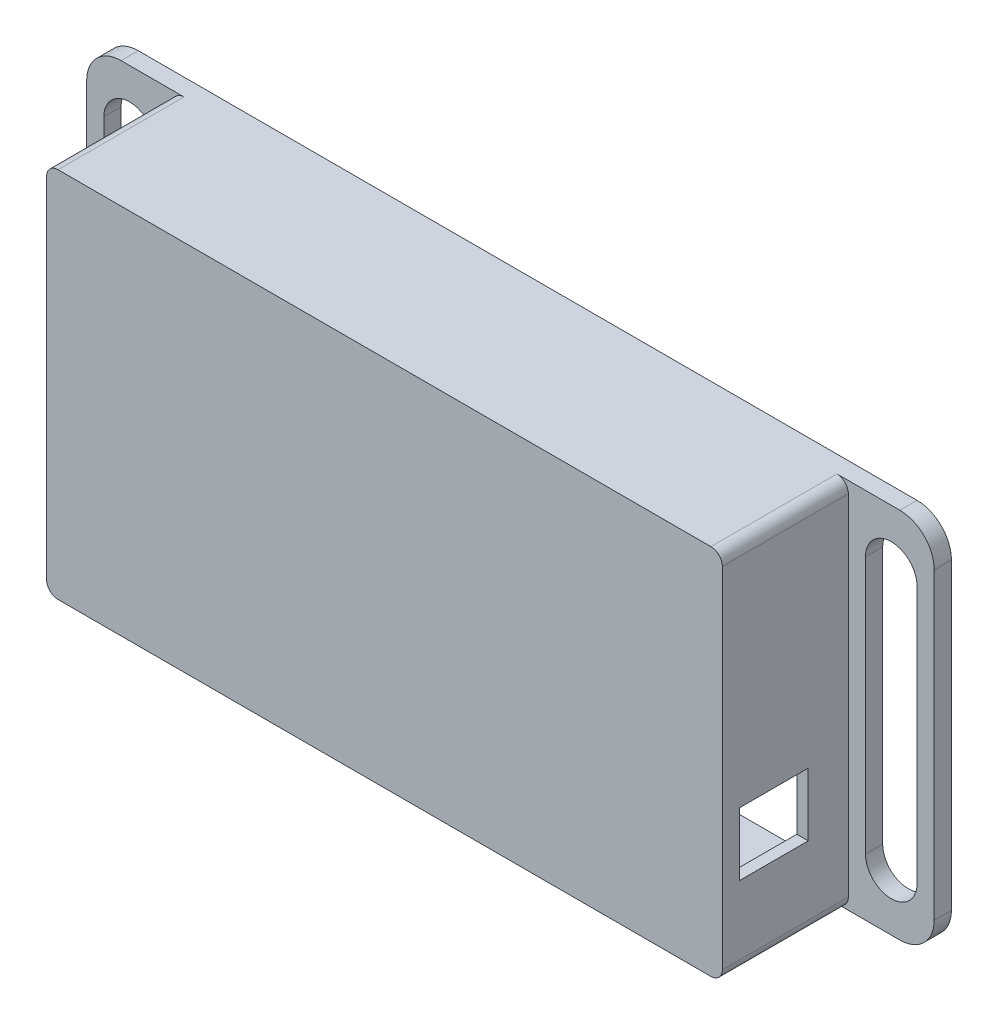
SolidWorks part; units mm, degrees
ref_plane "Front" through (0, 0, 0) normal (0, 0, 1) x (1, 0, 0)
ref_plane "Top" through (0, 0, 0) normal (0, 1, 0) x (1, 0, 0)
ref_plane "Right" through (0, 0, 0) normal (1, 0, 0) x (0, 0, -1)
sketch "Sketch1" plane through (0, 0, 0) normal (0, 0, 1) x (1, 0, 0)
  line L1 (-56.125, 30) -> (56.125, 30)
  line L2 (-56.125, 30) -> (-56.125, -30)
  line L3 (-56.125, -30) -> (56.125, -30)
  line L4 (56.125, 30) -> (56.125, -30)
  line L5 (-56.125, 30) -> (56.125, -30) construction
  line L6 (-56.125, -30) -> (56.125, 30) construction
  point P0 (0, 0)
  dimension "D1" = 112.25
  dimension "D2" = 60
sketch "Sketch2" plane through (0, 0, 0) normal (0, 0, 1) x (1, 0, 0)
  line L0 (-59, 32.5) -> (-59, -32.5)
  line L1 (-57, 30.5) -> (57, 30.5) construction
  line L2 (-57, 30.5) -> (-57, -30.5) construction
  line L3 (-57, -30.5) -> (57, -30.5) construction
  line L4 (57, 30.5) -> (57, -30.5) construction
  line L5 (-57, 30.5) -> (57, -30.5) construction
  line L6 (-57, -30.5) -> (57, 30.5) construction
  line L7 (-59, -32.5) -> (59, -32.5)
  line L8 (59, 32.5) -> (59, -32.5)
  line L9 (-59, 32.5) -> (59, 32.5)
  point P0 (0, 0)
  dimension "D1" = 61
  dimension "D2" = 114
  dimension "D3" = 2
extrude "Boss-Extrude2" add sketch "Sketch2" along normal blind 2
sketch "Sketch4" plane through (0, 0, 0) normal (0, 0, 1) x (1, 0, 0)
  line L0 (57, -30.5) -> (57, 30.5)
  line L1 (-59, -32.5) -> (59, -32.5)
  line L2 (-59, -32.5) -> (-59, 32.5)
  line L3 (-59, 32.5) -> (59, 32.5)
  line L4 (59, -32.5) -> (59, 32.5)
  line L5 (-57, 30.5) -> (57, 30.5)
  line L6 (-57, -30.5) -> (-57, 30.5)
  line L7 (-57, -30.5) -> (57, -30.5)
  dimension "D1" = 2
extrude "Boss-Extrude3" add sketch "Sketch4" against normal blind 23
sketch "Sketch6" plane through (0, 0, -23) normal (0, 0, -1) x (-1, 0, 0)
  line L0 (66.5, -22.5) -> (66.5, 22.5) construction
  line L1 (59, 32.5) -> (74, 32.5)
  line L2 (59, 32.5) -> (59, -32.5)
  line L3 (59, -32.5) -> (74, -32.5)
  line L4 (74, 32.5) -> (74, -32.5)
  line L5 (62, -22.5) -> (62, 22.5)
  line L6 (71, -22.5) -> (71, 22.5)
  line L7 (0, 0) -> (66.5, 0) construction
  line L8 (66.5, -22.5) -> (66.5, -32.5) construction
  arc A0 (62, -22.5) -> (71, -22.5) centre (66.5, -22.5) ccw
  arc A1 (71, 22.5) -> (62, 22.5) centre (66.5, 22.5) ccw
  point P8 (66.5, 0)
  dimension "D1" = 3
  dimension "D2" = 9
  dimension "D3" = 45
extrude "Boss-Extrude4" add sketch "Sketch6" against normal blind 3
fillet "Fillet1" radius 6 2 edges at (-74, -32.5, -21.5) (-74, 32.5, -21.5)
mirror "Mirror1" about plane through (0, 0, 0) normal (1, 0, 0) of "Fillet1", "Boss-Extrude4"
fillet "Fillet2" radius 2 4 edges
fillet "Fillet3" radius 1 4 edges at (-57, -30.5, -11.5) (-57, 30.5, -11.5) (57, 30.5, -11.5) (57, -30.5, -11.5)
sketch "Sketch7" plane through (59, 0, 0) normal (1, 0, 0) x (0, 0, -1)
  line L0 (0, -29.5) -> (0, 29.5) construction
  line L1 (1, -7.5) -> (13, -7.5)
  line L2 (1, -7.5) -> (1, -18.5)
  line L3 (1, -18.5) -> (13, -18.5)
  line L4 (13, -7.5) -> (13, -18.5)
  point P4 (0, 0)
  dimension "D1" = 1
  dimension "D2" = 12
  dimension "D3" = 11
  dimension "D4" = 7.5
extrude "Cut-Extrude1" cut sketch "Sketch7" against normal blind 10
